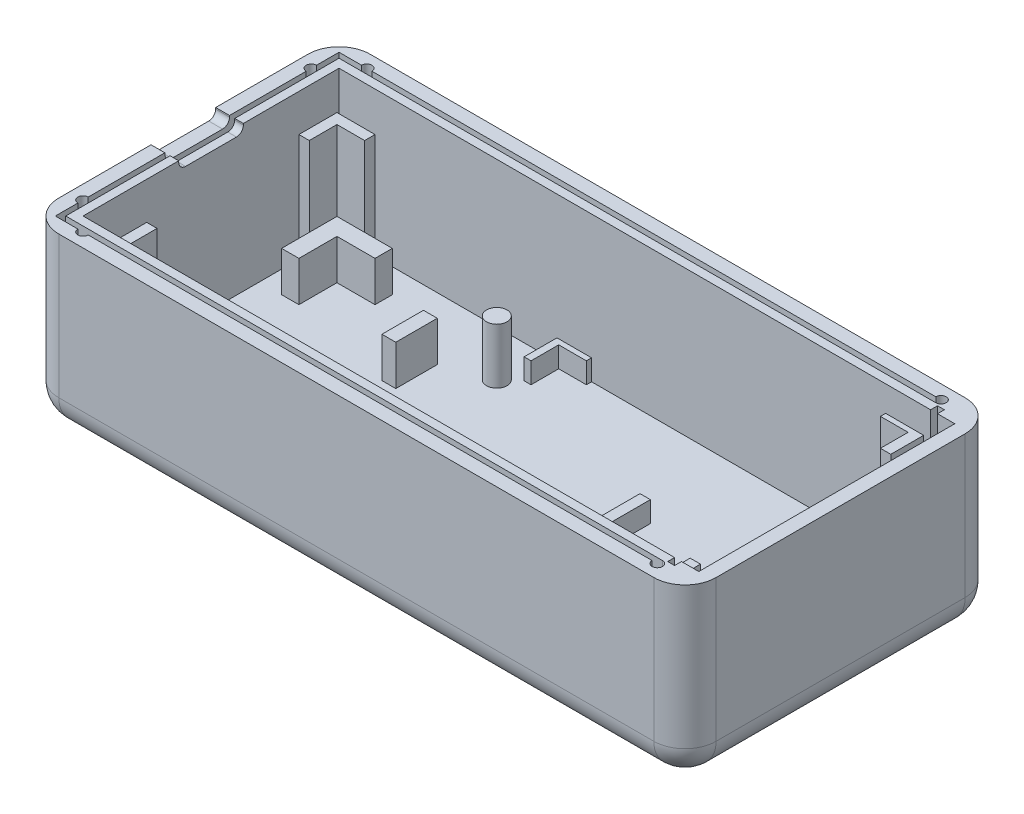
SolidWorks part; units mm, degrees
note: The reader was unsure of these and kept them because the rebuilt part matched: shared geometry of "Эскиз2<6>".
other "Исправление1"
sketch "Эскиз3"
other "Исправление2"
sketch "Эскиз4"
ref_plane "Спереди" through (0, 0, 0) normal (0, 0, 1) x (1, 0, 0)
ref_plane "Сверху" through (0, 0, 0) normal (0, 1, 0) x (1, 0, 0)
ref_plane "Справа" through (0, 0, 0) normal (1, 0, 0) x (0, 0, -1)
sketch "Эскиз1" plane through (0, 0, 0) normal (0, 1, 0) x (1, 0, 0)
  line L1 (0, 0) -> (95, 0)
  line L2 (0, 0) -> (0, -45)
  line L3 (0, -45) -> (95, -45)
  line L4 (95, 0) -> (95, -45)
  dimension "D1" = 45
  dimension "D2" = 95
extrude "Бобышка-Вытянуть1" add sketch "Эскиз1" along normal blind 25
shell "Оболочка1" thickness 4
fillet "Скругление1" radius 4.5 8 edges at (47.5, 0, 45) (95, 0, 22.5) (47.5, 0, 0) (0, 0, 22.5) (95, 12.5, 0) (95, 12.5, 45) (0, 12.5, 0) (0, 12.5, 45)
sketch "Эскиз2" plane through (0, 25, 0) normal (0, 1, 0) x (1, 0, 0)
  line L0 (47.5, -4) -> (47.5, -41) construction
  line L1 (91, -4) -> (4, -4) construction
  line L2 (4, -41) -> (91, -41) construction
  line L3 (4, -22.5) -> (91, -22.5) construction
  line L4 (4, -4) -> (4, -41) construction
  line L5 (91, -41) -> (91, -4) construction
  line L6 (90.5, 0) -> (4.5, 0) construction
  line L7 (4, -4) -> (4, -41) construction
  line L8 (91, -4) -> (4, -4) construction
  line L9 (2.75, -6) -> (2.75, -2.75)
  line L10 (6, -2.75) -> (2.75, -2.75)
  line L11 (2, -5.25) -> (2, -2)
  line L12 (2, -2) -> (5.25, -2)
  line L13 (92.25, -6) -> (92.25, -2.75)
  line L14 (93, -5.25) -> (93, -2)
  line L15 (89, -2.75) -> (92.25, -2.75)
  line L16 (93, -2) -> (89.75, -2)
  line L17 (93, -43) -> (89.75, -43)
  line L18 (89, -42.25) -> (92.25, -42.25)
  line L19 (93, -39.75) -> (93, -43)
  line L20 (92.25, -39) -> (92.25, -42.25)
  line L21 (2, -43) -> (5.25, -43)
  line L22 (2, -39.75) -> (2, -43)
  line L23 (6, -42.25) -> (2.75, -42.25)
  line L24 (2.75, -39) -> (2.75, -42.25)
  line L25 (2, -6.75) -> (2, -38.25)
  line L26 (2.75, -39) -> (2.75, -6)
  line L27 (6, -2.75) -> (89, -2.75)
  line L28 (88.25, -2) -> (6.75, -2)
  line L29 (93, -6.75) -> (93, -38.25)
  line L30 (92.25, -6) -> (92.25, -39)
  line L31 (89, -42.25) -> (6, -42.25)
  line L32 (6.75, -43) -> (88.25, -43)
  line L33 (92.25, -42.25) -> (92.25, -43)
  line L34 (92.25, -2.75) -> (92.25, -2)
  circle A0 centre (6, -2) radius 0.75
  circle A1 centre (2, -6) radius 0.75
  circle A2 centre (93, -6) radius 0.75
  circle A3 centre (89, -2) radius 0.75
  circle A4 centre (89, -43) radius 0.75
  circle A5 centre (93, -39) radius 0.75
  circle A6 centre (2, -39) radius 0.75
  circle A7 centre (6, -43) radius 0.75
  dimension "D1" = 1.5
  dimension "D4" = 1.5
  dimension "D2" = 2
  dimension "D3" = 2
  dimension "D5" = 2
  dimension "D6" = 2
extrude "Вырез-Вытянуть1" cut sketch "Эскиз2" against normal blind 5 contours A0 | A1 L9 L10 A0 L12 L11 | A1 | A4 | A3 | A6 | L21 A7 L23 L24 A6 L22 | A7
extrude "Вырез-Вытянуть3" cut sketch "Эскиз2<6>" against normal blind 2.5 contours L25 A6 L26 A1 | L27 A3 L28 A0 | L31 A7 L32 A4
sketch "Эскиз2<6>" plane through (0, 25, 0) normal (0, 1, 0) x (1, 0, 0) same geometry as "Эскиз2"
sketch "Эскиз7" plane through (0, 4, 0) normal (0, 1, 0) x (1, 0, 0)
  line L0 (91, -4) -> (4, -4) construction
  line L1 (89.5, -4) -> (90.5, -4)
  line L2 (89.5, -4) -> (89.5, -41)
  line L3 (89.5, -41) -> (90.5, -41)
  line L4 (90.5, -4) -> (90.5, -41)
  line L5 (4, -41) -> (91, -41) construction
  line L7 (95, -40.5) -> (95, -4.5) construction
  dimension "D1" = 1
  dimension "D2" = 4.5
sketch "Эскиз8" plane through (91, 0, 0) normal (-1, 0, 0) x (0, 0, 1)
  line L1 (5.5, 19.5) -> (39.5, 19.5)
  line L2 (5.5, 19.5) -> (5.5, 9.5)
  line L3 (5.5, 9.5) -> (39.5, 9.5)
  line L4 (39.5, 19.5) -> (39.5, 9.5)
  line L8 (22.5, 25) -> (22.5, 4.5) construction
  line L9 (4.5, 25) -> (40.5, 25) construction
  line L10 (4.5, 4.5) -> (40.5, 4.5) construction
  line L11 (4.5, 14.75) -> (40.5, 14.75) construction
  line L12 (4.5, 25) -> (4.5, 4.5) construction
  line L13 (40.5, 4.5) -> (40.5, 25) construction
  dimension "D1" = 17
  dimension "D2" = 17
  dimension "D3" = 4.75
  dimension "D4" = 5.25
extrude "Вырез-Вытянуть4" cut sketch "Эскиз8" against normal blind 3
sketch "Эскиз9" plane through (91, 0, 0) normal (-1, 0, 0) x (0, 0, 1)
  line L0 (4, 4) -> (4, 25)
  line L1 (4, 25) -> (41, 25)
  line L2 (41, 25) -> (41, 4)
  line L3 (41, 4) -> (4, 4)
extrude "Вырез-Вытянуть7" cut sketch "Эскиз9" against normal blind 2
extrude "Вырез-Вытянуть8" cut sketch "Эскиз7" against normal blind 1
sketch "Эскиз11" plane through (0, 0, 4) normal (0, 0, 1) x (1, 0, 0)
  line L0 (93, 25) -> (4, 25) construction
  line L1 (89.5, 4) -> (90.5, 4)
  line L2 (89.5, 4) -> (89.5, 25)
  line L3 (89.5, 25) -> (90.5, 25)
  line L4 (90.5, 4) -> (90.5, 25)
extrude "Вырез-Вытянуть10" cut sketch "Эскиз11" against normal blind 1
sketch "Эскиз12" plane through (0, 0, 41) normal (0, 0, -1) x (-1, 0, 0)
  line L0 (-4, 25) -> (-93, 25) construction
  line L1 (-90.5, 4) -> (-89.5, 4)
  line L2 (-90.5, 4) -> (-90.5, 25)
  line L3 (-90.5, 25) -> (-89.5, 25)
  line L4 (-89.5, 4) -> (-89.5, 25)
extrude "Вырез-Вытянуть11" cut sketch "Эскиз12" against normal blind 1
sketch "Эскиз15" plane through (94, 0, 0) normal (-1, 0, 0) x (0, 0, 1)
  line L0 (39.5, 19.5) -> (5.5, 19.5) construction
  line L1 (14.25, 19.5) -> (14.75, 19.5)
  line L2 (14.25, 19.5) -> (14.25, 9.5)
  line L3 (14.25, 9.5) -> (14.75, 9.5)
  line L4 (14.75, 19.5) -> (14.75, 9.5)
  line L5 (5.5, 9.5) -> (39.5, 9.5) construction
  line L7 (5.5, 9.5) -> (39.5, 9.5) construction
  line L8 (22.25, 19.5) -> (22.75, 19.5)
  line L9 (22.25, 19.5) -> (22.25, 9.5)
  line L10 (22.25, 9.5) -> (22.75, 9.5)
  line L11 (22.75, 19.5) -> (22.75, 9.5)
  line L12 (22.5, 25) -> (22.5, 4.5) construction
  line L13 (30.25, 19.5) -> (30.75, 19.5)
  line L14 (30.25, 19.5) -> (30.25, 9.5)
  line L15 (30.25, 9.5) -> (30.75, 9.5)
  line L16 (30.75, 19.5) -> (30.75, 9.5)
  line L17 (40.5, 25) -> (4.5, 25) construction
  line L18 (40.5, 4.5) -> (4.5, 4.5) construction
  dimension "D1" = 0.5
  dimension "D2" = 7.75
  dimension "D3" = 7.75
  dimension "D4" = 0.5
  dimension "D5" = 0.5
  dimension "D6" = 7.75
  dimension "D7" = 0.25
extrude "Бобышка-Вытянуть2" add sketch "Эскиз15" along normal blind 1
sketch "Эскиз17" plane through (0, 4, 0) normal (0, 1, 0) x (1, 0, 0)
  line L0 (88.5, -4) -> (88.5, -41) construction
  line L1 (89.5, -4) -> (4, -4) construction
  line L2 (4, -41) -> (89.5, -41) construction
  line L3 (89.5, -4) -> (89.5, -41) construction
  line L4 (34, -4) -> (34, -41) construction
  line L5 (4, -41) -> (89.5, -41) construction
  line L6 (4, -4) -> (4, -41) construction
  line L7 (90.5, -22.5) -> (4, -22.5) construction
  line L8 (90.5, -41) -> (90.5, -4) construction
  line L9 (4, -4) -> (4, -41) construction
  line L10 (62.5, -4.75) -> (87, -4.75) construction
  line L11 (36.5, -4.75) -> (61, -4.75) construction
  line L12 (36.5, -4.75) -> (36.5, -40.25) construction
  line L13 (36.5, -40.25) -> (61, -40.25) construction
  line L14 (61, -4.75) -> (61, -40.25) construction
  line L15 (62.5, -4.75) -> (62.5, -40.25) construction
  line L16 (87, -4.75) -> (87, -40.25) construction
  line L17 (62.5, -40.25) -> (87, -40.25) construction
  line L19 (36.5, -12.5) -> (29.5, -12.5) construction
  line L20 (36.5, -12.5) -> (36.5, -32.5) construction
  line L21 (36.5, -32.5) -> (29.5, -32.5) construction
  line L22 (29.5, -12.5) -> (29.5, -32.5) construction
  line L25 (61, -17.5) -> (62.5, -17.5)
  line L30 (83, -3.75) -> (83, -4.75)
  line L31 (83, -4.75) -> (87, -4.75)
  line L32 (87, -4.75) -> (87, -8.75)
  line L33 (87, -8.75) -> (88.5, -8.75)
  line L34 (88.5, -8.75) -> (88.5, -3.75)
  line L35 (88.5, -3.75) -> (83, -3.75)
  line L36 (40.5, -3.75) -> (35.5, -3.75)
  line L37 (35.5, -3.75) -> (35.5, -8.75)
  line L38 (35.5, -8.75) -> (36.5, -8.75)
  line L39 (36.5, -8.75) -> (36.5, -4.75)
  line L40 (36.5, -4.75) -> (40.5, -4.75)
  line L41 (40.5, -4.75) -> (40.5, -3.75)
  line L42 (61, -17.5) -> (61, -27.5)
  line L43 (61, -27.5) -> (62.5, -27.5)
  line L44 (62.5, -27.5) -> (62.5, -17.5)
  line L45 (87, -36.25) -> (88.5, -36.25)
  line L46 (87, -40.25) -> (87, -36.25)
  line L47 (88.5, -36.25) -> (88.5, -41.25)
  line L48 (83, -40.25) -> (87, -40.25)
  line L49 (88.5, -41.25) -> (83, -41.25)
  line L50 (83, -41.25) -> (83, -40.25)
  line L51 (40.5, -40.25) -> (40.5, -41.25)
  line L52 (35.5, -36.25) -> (36.5, -36.25)
  line L53 (36.5, -36.25) -> (36.5, -40.25)
  line L54 (36.5, -40.25) -> (40.5, -40.25)
  line L55 (40.5, -41.25) -> (35.5, -41.25)
  line L56 (35.5, -41.25) -> (35.5, -36.25)
  point P24 (36.5, -22.5)
  point P25 (29.5, -22.5)
  point P41 (61, -22.5)
  dimension "D1" = 1
  dimension "D2" = 30
  dimension "D3" = 24.5
  dimension "D4" = 35.5
  dimension "D6" = 7
  dimension "D7" = 20
  dimension "D8" = 1.5
  dimension "D9" = 1.5
  dimension "D10" = 5
  dimension "D11" = 1
  dimension "D12" = 4
  dimension "D13" = 1
  dimension "D14" = 4
  dimension "D16" = 1.5
  dimension "D20" = 1.5
  dimension "D21" = 4
  dimension "D5" = 2
extrude "Бобышка-Вытянуть3" add sketch "Эскиз17" along normal blind 3
sketch "Эскиз18" plane through (0, 4, 0) normal (0, 1, 0) x (1, 0, 0)
  line L0 (4, -22.5) -> (89.5, -22.5) construction
  line L1 (4, -4) -> (4, -41) construction
  line L2 (89.5, -4) -> (89.5, -41) construction
  line L3 (35.5, -4) -> (35.5, -8.75) construction
  circle A0 centre (33.4, -10.6) radius 1.485
  circle A1 centre (33.4, -34.4) radius 1.485
  dimension "D1" = 2.97
  dimension "D2" = 23.8
  dimension "D3" = 2.1
extrude "Бобышка-Вытянуть4" add sketch "Эскиз18" along normal blind 8
sketch "Эскиз19" plane through (0, 0, 0) normal (-1, 0, 0) x (0, 0, 1)
  line L0 (22.5, 25) -> (22.5, 4.5) construction
  line L1 (4.5, 25) -> (40.5, 25) construction
  line L2 (4.5, 4.5) -> (40.5, 4.5) construction
  line L4 (17.83, 25) -> (27.17, 25)
  line L5 (17.83, 25) -> (17.83, 23.8)
  line L6 (17.83, 23.8) -> (27.17, 23.8)
  line L7 (27.17, 25) -> (27.17, 23.8)
  dimension "D1" = 1.2
  dimension "D2" = 4.67
  dimension "D3" = 4.67
extrude "Вырез-Вытянуть12" cut sketch "Эскиз19" against normal blind 10
fillet "Скругление2" radius 1 1 edges at (1, 23.8, 27.17)
fillet "Скругление3" radius 1 1 edges at (3.375, 23.8, 27.17)
fillet "Скругление4" radius 1 1 edges at (3.375, 23.8, 17.83)
fillet "Скругление5" radius 1 1 edges at (1, 23.8, 17.83)
sketch "Эскиз20" plane through (0, 4, 0) normal (0, 1, 0) x (1, 0, 0)
  line L0 (4, -22.5) -> (89.5, -22.5) construction
  line L1 (7.2, -7.5) -> (30.2, -7.5) construction
  line L2 (7.2, -7.5) -> (7.2, -37.5) construction
  line L3 (7.2, -37.5) -> (30.2, -37.5) construction
  line L4 (30.2, -7.5) -> (30.2, -37.5) construction
  line L5 (4, -4) -> (4, -41) construction
  line L6 (89.5, -4) -> (89.5, -41) construction
  line L13 (15.2, -10) -> (9.7, -10)
  line L14 (9.7, -10) -> (9.7, -15.5)
  line L17 (7.2, -15.5) -> (7.2, -7.5)
  line L18 (7.2, -7.5) -> (15.2, -7.5)
  line L20 (9.7, -29.5) -> (9.7, -35)
  line L21 (9.7, -35) -> (15.2, -35)
  line L25 (7.2, -29.5) -> (7.2, -37.5)
  line L26 (7.2, -37.5) -> (15.2, -37.5)
  line L27 (15.2, -10) -> (15.2, -7.5)
  line L28 (27.2, -13) -> (25.2, -13)
  line L29 (27.2, -13) -> (27.2, -19)
  line L30 (27.2, -19) -> (25.2, -19)
  line L31 (25.2, -13) -> (25.2, -19)
  line L32 (25.2, -26) -> (27.2, -26)
  line L33 (25.2, -26) -> (25.2, -32)
  line L34 (25.2, -32) -> (27.2, -32)
  line L35 (27.2, -26) -> (27.2, -32)
  line L36 (7.2, -15.5) -> (9.7, -15.5)
  line L37 (7.2, -29.5) -> (9.7, -29.5)
  line L38 (15.2, -35) -> (15.2, -37.5)
  dimension "D4" = 3.2
  dimension "D1" = 15
  dimension "D2" = 30
  dimension "D3" = 23
  dimension "D5" = 2.5
  dimension "D6" = 2.5
  dimension "D7" = 8
  dimension "D8" = 8
  dimension "D9" = 8
  dimension "D10" = 2.5
  dimension "D14" = 7
  dimension "D15" = 3.5
  dimension "D16" = 2
  dimension "D17" = 6
  dimension "D18" = 6
  dimension "D19" = 3
extrude "Бобышка-Вытянуть5" add sketch "Эскиз20" along normal blind 5.8
sketch "Эскиз22" plane through (0, 4, 0) normal (0, 1, 0) x (1, 0, 0)
  line L0 (7.2, -7.5) -> (7.2, -11.5)
  line L1 (7.2, -7.5) -> (7.2, -15.5) construction
  line L2 (7.2, -11.5) -> (5.7, -11.5)
  line L3 (5.7, -11.5) -> (5.7, -6)
  line L4 (5.7, -6) -> (11.2, -6)
  line L5 (11.2, -6) -> (11.2, -7.5)
  line L6 (15.2, -7.5) -> (7.2, -7.5) construction
  line L7 (11.2, -7.5) -> (7.2, -7.5)
  line L8 (15.2, -7.5) -> (7.2, -7.5) construction
  line L9 (7.2, -33.5) -> (5.7, -33.5)
  line L10 (7.2, -29.5) -> (7.2, -37.5) construction
  line L11 (5.7, -33.5) -> (5.7, -39)
  line L12 (5.7, -39) -> (11.2, -39)
  line L13 (11.2, -39) -> (11.2, -37.5)
  line L14 (7.2, -37.5) -> (15.2, -37.5) construction
  line L15 (11.2, -37.5) -> (7.2, -37.5)
  line L16 (7.2, -37.5) -> (7.2, -33.5)
  dimension "D1" = 1.5
  dimension "D2" = 1.5
  dimension "D3" = 1.5
  dimension "D4" = 1.5
extrude "Бобышка-Вытянуть6" add sketch "Эскиз22" along normal blind 17.3
sketch "Эскиз25" plane through (0, 7, 0) normal (0, 1, 0) x (1, 0, 0)
  line L0 (83, -4) -> (83, -4.75)
  line L1 (83, -4.75) -> (87, -4.75)
  line L2 (87, -4.75) -> (87, -8.75)
  line L3 (87, -8.75) -> (88.5, -8.75)
  line L4 (88.5, -8.75) -> (88.5, -4)
  line L5 (88.5, -4) -> (83, -4)
  line L6 (83, -40.25) -> (83, -41)
  line L7 (83, -41) -> (88.5, -41)
  line L8 (88.5, -41) -> (88.5, -36.25)
  line L9 (88.5, -36.25) -> (87, -36.25)
  line L10 (87, -36.25) -> (87, -40.25)
  line L11 (87, -40.25) -> (83, -40.25)
extrude "Бобышка-Вытянуть7" add sketch "Эскиз25" along normal blind 14.3
sketch "Эскиз26" plane through (0, 0, 0) normal (0, -1, 0) x (1, 0, 0)
  line L0 (4.5, 22.5) -> (90.5, 22.5) construction
  line L1 (4.5, 40.5) -> (4.5, 4.5) construction
  line L2 (90.5, 4.5) -> (90.5, 40.5) construction
  line L3 (47.5, 40.5) -> (47.5, 4.5) construction
  line L4 (90.5, 40.5) -> (4.5, 40.5) construction
  line L5 (4.5, 4.5) -> (90.5, 4.5) construction
  line L7 (34, 30.8) -> (61, 30.8) construction
  line L8 (34, 30.8) -> (34, 14.2) construction
  line L9 (34, 14.2) -> (61, 14.2) construction
  line L10 (61, 30.8) -> (61, 14.2) construction
  line L11 (34, 24.95) -> (49, 24.95)
  line L12 (34, 24.95) -> (34, 20.05)
  line L13 (34, 20.05) -> (49, 20.05)
  line L14 (49, 24.95) -> (49, 20.05)
  point P16 (47.5, 30.8)
  point P17 (34, 22.5)
  point P22 (34, 22.5)
  dimension "D1" = 27
  dimension "D2" = 16.6
  dimension "D3" = 4.9
  dimension "D4" = 15
extrude "Бобышка-Вытянуть8" add sketch "Эскиз26" along normal blind 2.4
sketch "Эскиз27" plane through (0, 0, 0) normal (0, -1, 0) x (1, 0, 0)
  line L0 (47.5, 40.5) -> (47.5, 4.5) construction
  line L1 (90.5, 40.5) -> (4.5, 40.5) construction
  line L2 (4.5, 4.5) -> (90.5, 4.5) construction
  line L3 (4.5, 22.5) -> (90.5, 22.5) construction
  line L4 (4.5, 40.5) -> (4.5, 4.5) construction
  line L5 (90.5, 4.5) -> (90.5, 40.5) construction
  line L6 (49, 20.05) -> (49, 24.95) construction
  line L7 (34, 30.8) -> (61, 30.8) construction
  line L8 (34, 30.8) -> (34, 14.2) construction
  line L9 (34, 14.2) -> (61, 14.2) construction
  line L10 (61, 30.8) -> (61, 14.2) construction
  line L11 (61, 30.8) -> (49, 30.8)
  line L12 (61, 30.8) -> (61, 26.4)
  line L13 (61, 26.4) -> (49, 26.4)
  line L14 (49, 30.8) -> (49, 26.4)
  line L15 (61, 14.2) -> (49, 14.2)
  line L16 (61, 14.2) -> (61, 18.7)
  line L17 (61, 18.7) -> (49, 18.7)
  line L18 (49, 14.2) -> (49, 18.7)
  point P17 (34, 22.5)
  point P18 (47.5, 30.8)
  dimension "D1" = 27
  dimension "D2" = 16.6
  dimension "D3" = 4.4
  dimension "D4" = 4.5
extrude "Бобышка-Вытянуть9" add sketch "Эскиз27" along normal blind 4.6
